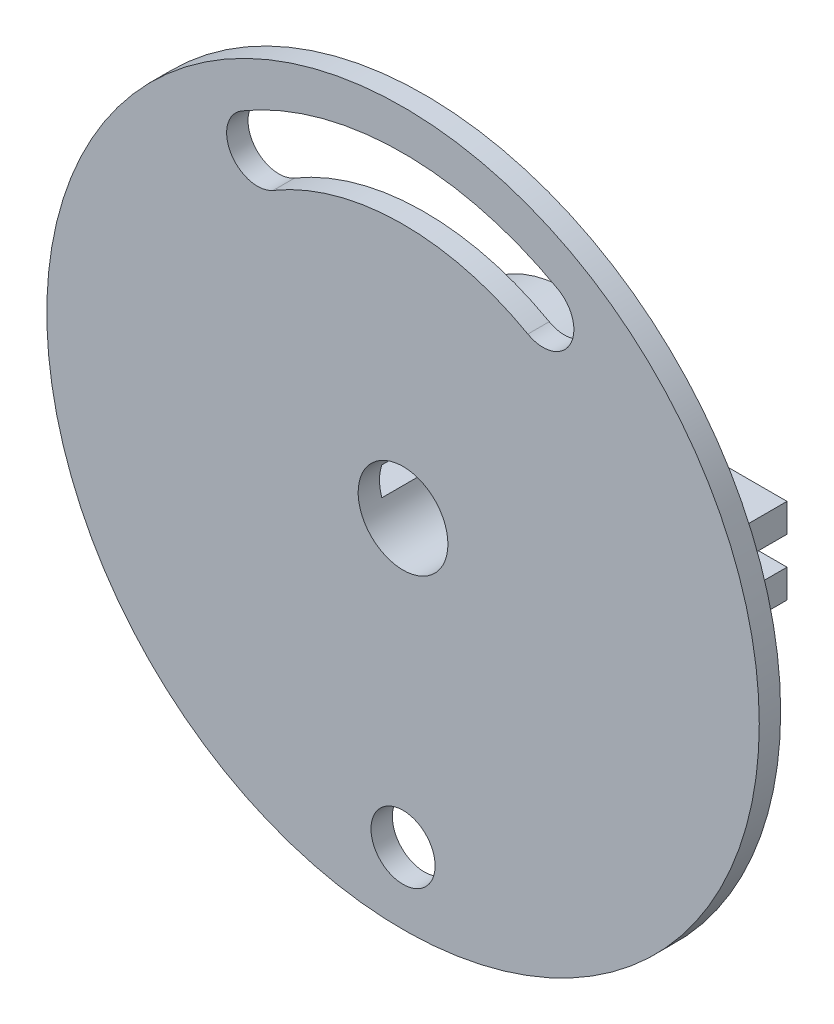
SolidWorks part; units mm, degrees
ref_plane "Front Plane" through (0, 0, 0) normal (0, 0, 1) x (1, 0, 0)
ref_plane "Top Plane" through (0, 0, 0) normal (0, 1, 0) x (1, 0, 0)
ref_plane "Right Plane" through (0, 0, 0) normal (1, 0, 0) x (0, 0, -1)
sketch "Sketch1" plane through (0, 0, 0) normal (0, 0, 1) x (1, 0, 0)
  line L0 (-27.0565, 7.3948) -> (22.9435, 7.3948) construction
  line L1 (-2.2565, 25.1948) -> (-2.2565, 29.5948) construction
  line L2 (-2.0565, 7.3948) -> (-2.2565, 25.1948)
  line L3 (-2.0565, 7.3948) -> (-11.1634, 22.7669)
  line L4 (-11.1634, 22.7669) -> (-13.3722, 26.4954)
  circle A0 centre (-2.0565, 7.3948) radius 25
  circle A2 centre (-2.0565, -12.6052) radius 2.25
  circle A7 centre (-2.0565, 7.3948) radius 3.15
  arc A9 (-11.1634, 22.7669) -> (-2.2565, 25.2609) centre (-2.0565, 7.3948) cw
  arc A10 (-2.2565, 29.5948) -> (-13.3722, 26.4954) centre (-2.0565, 7.3948) ccw
  arc A11 (-13.3722, 26.4954) -> (-11.1634, 22.7669) centre (-12.2678, 24.6312) ccw
  arc A12 (-2.3553, 29.5937) -> (8.8273, 26.7449) centre (-2.0565, 7.3948) cw
  arc A13 (6.7027, 22.9677) -> (-2.258, 25.2609) centre (-2.0565, 7.3948) ccw
  arc A14 (8.8273, 26.7449) -> (6.7027, 22.9677) centre (7.765, 24.8563) cw
  point P2 (-2.2565, 27.3948)
  dimension "D1" = 4.5
  dimension "D2" = 50
  dimension "D4" = 6.3
  dimension "D3" = 20
  dimension "D5" = 4.4
  dimension "D6" = 20
  dimension "D7" = 30
extrude "Boss-Extrude1" add sketch "Sketch1" along normal blind 1.5 contours A0 A2 A12 A14 A13 A9 A7 A11 A10 region at (-26.3494, 7.3948, 0)
sketch "Sketch2" plane through (0, 0, 0) normal (0, 0, -1) x (-1, 0, 0)
  line L0 (-13.3892, 10.3948) -> (-5.5213, 10.3948)
  line L1 (-13.3892, 4.3948) -> (-5.5213, 4.3948)
  line L2 (-13.3892, 10.3948) -> (-13.3892, 8.3948)
  line L3 (17.882, 10.3948) -> (17.882, 8.3948)
  line L4 (-13.3892, 8.3948) -> (-6.0319, 8.3948)
  line L6 (17.882, 6.3948) -> (5.0435, 6.3948)
  line L8 (-13.3892, 6.3948) -> (-13.3892, 4.3948)
  line L9 (9.6342, 10.3948) -> (17.882, 10.3948)
  line L10 (5.0435, 8.3948) -> (17.882, 8.3948)
  line L11 (17.882, 6.3948) -> (17.882, 4.3948)
  line L12 (9.6342, 4.3948) -> (17.882, 4.3948)
  line L13 (-0.9306, 6.3948) -> (-13.3892, 6.3948)
  line L14 (-6.0319, 8.3948) -> (-0.9306, 8.3948)
  arc A0 (5.0435, 8.3948) -> (-0.9306, 8.3948) centre (2.0565, 7.3948) ccw
  arc A2 (9.6342, 10.3948) -> (-5.5213, 10.3948) centre (2.0565, 7.3948) ccw
  arc A3 (-5.5213, 4.3948) -> (9.6342, 4.3948) centre (2.0565, 7.3948) ccw
  arc A4 (-0.9306, 6.3948) -> (5.0435, 6.3948) centre (2.0565, 7.3948) ccw
  dimension "D2" = 3
  dimension "D3" = 3
  dimension "D4" = 2
  dimension "D5" = 2
extrude "Boss-Extrude2" add sketch "Sketch2" along normal blind 10
sketch "Sketch4" plane through (0, 10.3948, 0) normal (0, 1, 0) x (1, 0, 0)
  line L1 (-17.882, 10) -> (-17.882, 0) construction
  line L2 (13.3892, 10) -> (13.3892, 0) construction
  line L3 (5.5213, 10) -> (13.3892, 10) construction
  line L4 (-17.882, 10) -> (-9.6342, 10) construction
  circle A0 centre (9.2642, 5) radius 1.1
  circle A1 centre (-13.757, 5) radius 1.1
  dimension "D1" = 4.125
  dimension "D2" = 4.125
  dimension "D3" = 5
  dimension "D4" = 5
extrude "Cut-Extrude1" cut sketch "Sketch4" against normal through all
